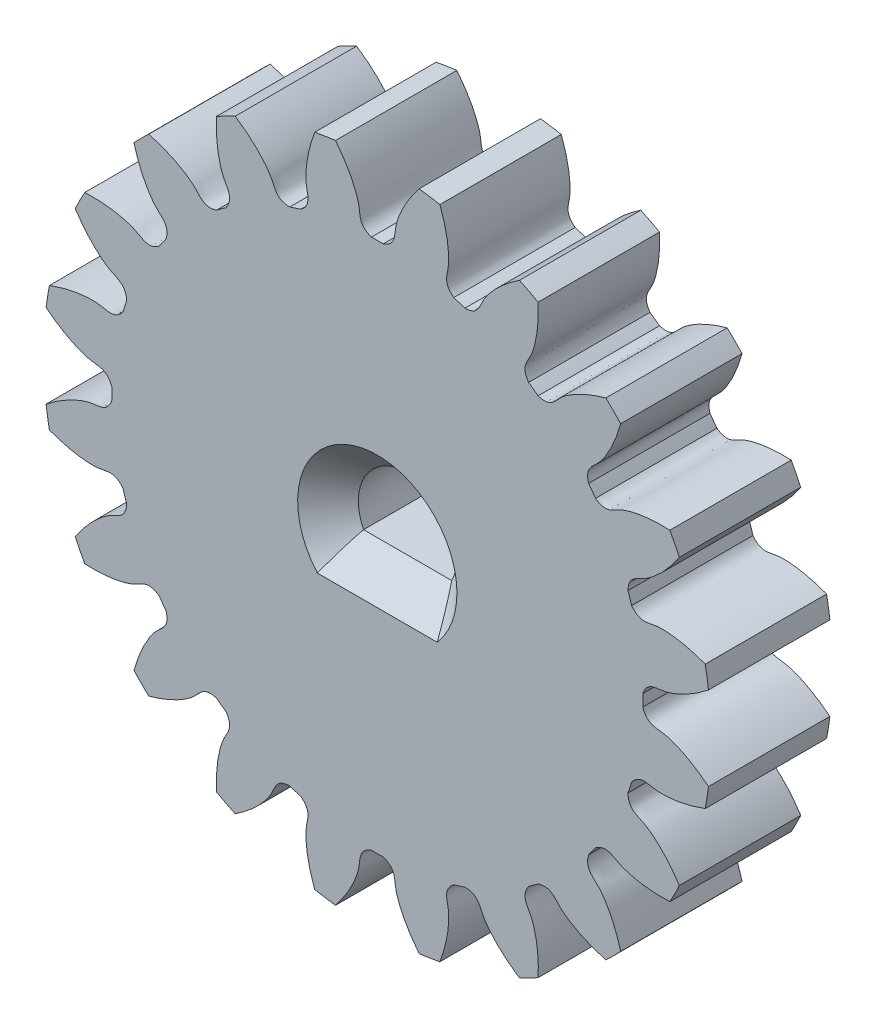
SolidWorks part; units mm, degrees
ref_plane "前视基准面" through (0, 0, 0) normal (0, 0, 1) x (1, 0, 0)
ref_plane "上视基准面" through (0, 0, 0) normal (0, 1, 0) x (1, 0, 0)
ref_plane "右视基准面" through (0, 0, 0) normal (1, 0, 0) x (0, 0, -1)
sketch "草图1" plane through (0, 0, 0) normal (0, 0, 1) x (1, 0, 0)
  circle A0 centre (0, 0) radius 11
extrude "凸台-拉伸1" add sketch "草图1" along normal blind 4
ref_axis "基准轴1" through (0, 0, -1.5) along (0, 0, 1)
sketch "草图2" plane through (0, 0, 0) normal (0, 0, 1) x (1, 0, 0)
  line L0 (0, 0) -> (0, 11) construction
  circle A0 centre (0, 0) radius 11 construction
  arc A1 (0.1933, 8.7479) -> (-0.1933, 8.7479) centre (0, 0) ccw
  arc A2 (3.1812, 12.4983) -> (-3.1812, 12.4983) centre (0, 0) ccw
  spline S0 degree 3 poles (0.1933, 8.7479) (0.6112, 8.8935) (0.5571, 9.1871) (0.6129, 9.47) (0.6189, 9.4976) (0.6263, 9.5286) (0.6353, 9.5632) (0.646, 9.6012) (0.6585, 9.6426) (0.673, 9.6873) (0.6897, 9.7352) (0.7086, 9.7863) (0.7299, 9.8406) (0.7537, 9.8978) (0.7801, 9.958) (0.8094, 10.0211) (0.8415, 10.087) (0.8767, 10.1556) (0.915, 10.2267) (0.9566, 10.3004) (1.0015, 10.3764) (1.05, 10.4548) (1.102, 10.5352) (1.1578, 10.6178) (1.2173, 10.7023) (1.2808, 10.7886) (1.3482, 10.8766) (1.4198, 10.9662) (1.4955, 11.0572) (1.5755, 11.1496) (1.6598, 11.2431) (1.7486, 11.3376) (1.8418, 11.4331) (1.9397, 11.5293) (2.0421, 11.6261) (2.1493, 11.7233) (2.2612, 11.8209) (2.378, 11.9186) (2.4996, 12.0163) (2.6261, 12.1139) (2.7575, 12.2112) (2.9415, 12.3416) (3.0839, 12.4363) (3.1812, 12.4983) knots 0 0 0 0 0.165916 0.170906 0.176664 0.183189 0.190482 0.198542 0.207371 0.216967 0.22733 0.238462 0.250361 0.263027 0.276462 0.290664 0.305634 0.321371 0.337876 0.355149 0.37319 0.391998 0.411574 0.431917 0.453028 0.474907 0.497554 0.520968 0.54515 0.570099 0.595817 0.622302 0.649554 0.677575 0.706363 0.735918 0.766242 0.797333 0.829191 0.861818 0.895212 0.929373 1 1 1 1
  spline S1 degree 3 poles (-0.1933, 8.7479) (-0.6112, 8.8935) (-0.5571, 9.1871) (-0.6129, 9.47) (-0.6189, 9.4976) (-0.6263, 9.5286) (-0.6353, 9.5632) (-0.646, 9.6012) (-0.6585, 9.6426) (-0.673, 9.6873) (-0.6897, 9.7352) (-0.7086, 9.7863) (-0.7299, 9.8406) (-0.7537, 9.8978) (-0.7801, 9.958) (-0.8094, 10.0211) (-0.8415, 10.087) (-0.8767, 10.1556) (-0.915, 10.2267) (-0.9566, 10.3004) (-1.0015, 10.3764) (-1.05, 10.4548) (-1.102, 10.5352) (-1.1578, 10.6178) (-1.2173, 10.7023) (-1.2808, 10.7886) (-1.3482, 10.8766) (-1.4198, 10.9662) (-1.4955, 11.0572) (-1.5755, 11.1496) (-1.6598, 11.2431) (-1.7486, 11.3376) (-1.8418, 11.4331) (-1.9397, 11.5293) (-2.0421, 11.6261) (-2.1493, 11.7233) (-2.2612, 11.8209) (-2.378, 11.9186) (-2.4996, 12.0163) (-2.6261, 12.1139) (-2.7575, 12.2112) (-2.9415, 12.3416) (-3.0839, 12.4363) (-3.1812, 12.4983) knots 0 0 0 0 0.165916 0.170906 0.176664 0.183189 0.190482 0.198542 0.207371 0.216967 0.22733 0.238462 0.250361 0.263027 0.276462 0.290664 0.305634 0.321371 0.337876 0.355149 0.37319 0.391998 0.411574 0.431917 0.453028 0.474907 0.497554 0.520968 0.54515 0.570099 0.595817 0.622302 0.649554 0.677575 0.706363 0.735918 0.766242 0.797333 0.829191 0.861818 0.895212 0.929373 1 1 1 1
extrude "切除-拉伸1" cut sketch "草图2" along normal through all
pattern_circular "阵列(圆周)1" count 20 every 18 about axis through (0, 0, -1.5) along (0, 0, 1) of "切除-拉伸1"
sketch "草图3" plane through (0, 0, 0) normal (0, 0, 1) x (1, 0, 0)
  circle A0 centre (0, 0) radius 10 construction
  dimension "Dn" = 20
sketch "草图4" plane through (0, 0, 4) normal (0, 0, 1) x (1, 0, 0)
  line L0 (-1.4518, -0.73) -> (1.4518, -0.73)
  arc A0 (1.4518, -0.73) -> (-1.4518, -0.73) centre (0, 0) ccw
  dimension "D1" = 3.25
  dimension "D2" = 0.73
extrude "切除-拉伸2" cut sketch "草图4" against normal blind 10
sketch "草图5" plane through (0, 0, 4) normal (0, 0, 1) x (1, 0, 0)
  circle A0 centre (0, 0) radius 1.6
  circle A1 centre (0, 0) radius 2.5
  dimension "D1" = 3.2
  dimension "D2" = 5
extrude "凸台-拉伸2" [suppressed] add sketch "草图5" along normal blind 1.5
sketch "草图6" plane through (0, 0, 0) normal (0, 0, -1) x (-1, 0, 0)
  line L1 (-1.4518, -0.73) -> (1.4518, -0.73)
  line L2 (-1.4518, -0.73) -> (1.4518, -0.73)
  circle A0 centre (0, 0) radius 2.25
  arc A1 (1.4518, -0.73) -> (-1.4518, -0.73) centre (0, 0) ccw
  arc A2 (1.4518, -0.73) -> (-1.4518, -0.73) centre (0, 0) ccw
  dimension "D2" = 4.5
  dimension "D1" = 0
extrude "凸台-拉伸3" add sketch "草图6" along normal blind 1.5
sketch "草图7" plane through (0, 0, 0) normal (0, 0, -1) x (-1, 0, 0)
  circle A0 centre (0, 0) radius 5.5
  dimension "D1" = 11
extrude "切除-拉伸-薄壁1" cut sketch "草图7" against normal blind 1.5 thin thin type mid plane wall 3
chamfer "倒角1" distance 1 angle 45 2 edges at (0, 1.625, 4) (0, -0.73, 4)
